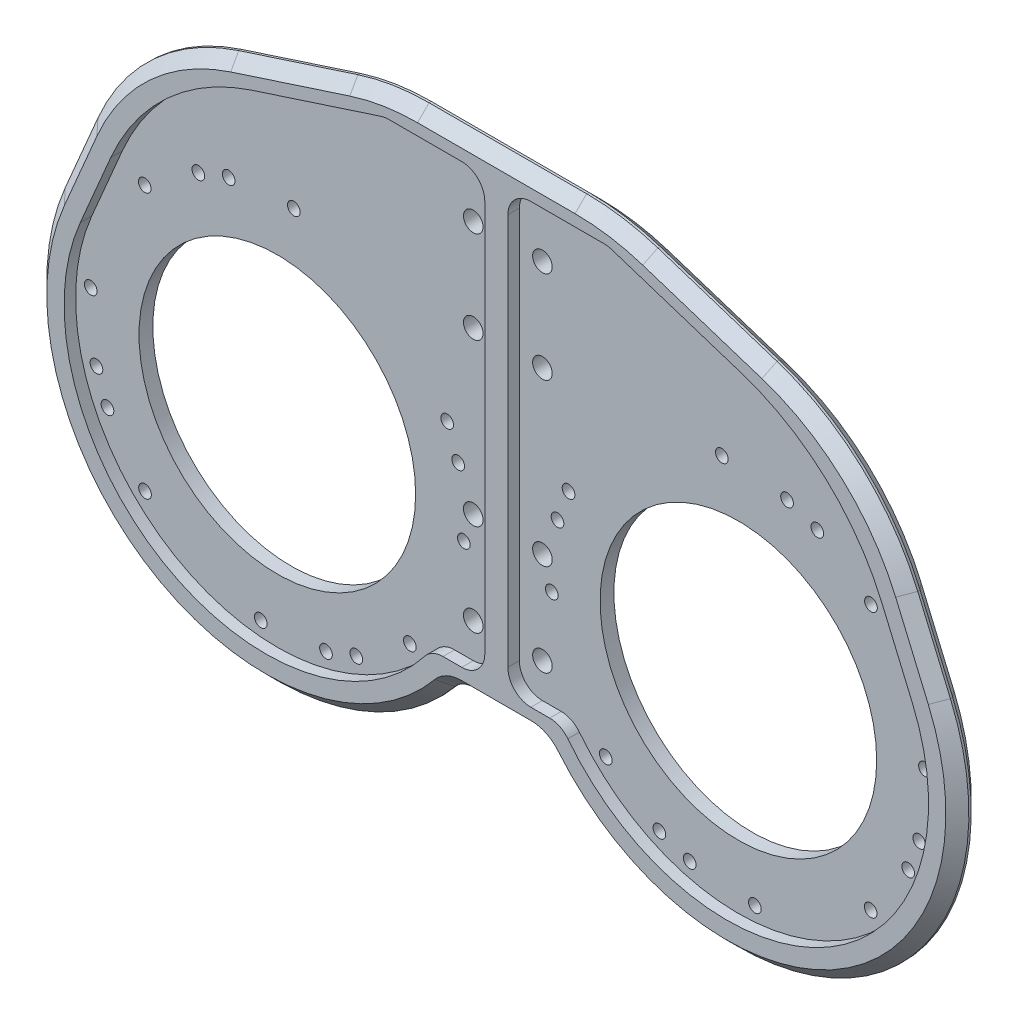
SolidWorks part; units mm, degrees
material "6061 合金"
ref_plane "前视基准面" through (0, 0, 0) normal (0, 0, 1) x (1, 0, 0)
ref_plane "上视基准面" through (0, 0, 0) normal (0, 1, 0) x (1, 0, 0)
ref_plane "右视基准面" through (0, 0, 0) normal (1, 0, 0) x (0, 0, -1)
other "Configuration Table"
sketch "草图1" plane through (0, 0, 0) normal (0, 0, 1) x (1, 0, 0)
  line L0 (0, 0) -> (0, 250) construction
  line L1 (0, 250) -> (769.4209, 0)
  line L3 (769.4209, 0) -> (0, 0)
  line L4 (-50, 352.899) -> (-50, -139.8009) construction
  line L5 (-869.4209, 0) -> (-100, 0)
  line L6 (-100, 250) -> (-869.4209, 0)
  line L7 (-100, 0) -> (-100, 250) construction
  line L8 (-100, 250) -> (0, 250)
  line L9 (0, 0) -> (-100, 0)
  circle A0 centre (50, 100) radius 85 construction
  circle A1 centre (50, 100) radius 60
  circle A2 centre (-150, 100) radius 85 construction
  circle A3 centre (-150, 100) radius 60
  dimension "D1" = 170
  dimension "D4" = 120
  dimension "D2" = 100
  dimension "D3" = 72
  dimension "D5" = 250
  dimension "D6" = 100
  dimension "D7" = 50
extrude "凸台-拉伸1" add sketch "草图1" along normal blind 6 contours L9 L3 L1 L8 L6 L5 A1 A3 region at (-50, 86.7466, 0)
sketch "草图4" plane through (0, 0, 6) normal (0, 0, 1) x (1, 0, 0)
  line L0 (-50, 330.4726) -> (-50, -61.6586) construction
  arc A0 (259.7806, 158.4465) -> (255.249, 156.3335) centre (257.5148, 157.39) ccw construction
  arc A1 (278.6673, 106.1128) -> (283.1989, 108.2258) centre (280.9331, 107.1693) ccw construction
  arc A2 (276.1928, 77.8292) -> (280.7244, 79.9423) centre (278.4586, 78.8857) ccw construction
  arc A3 (271.409, 64.6857) -> (275.9405, 66.7988) centre (273.6748, 65.7423) ccw construction
  arc A4 (255.1242, 41.4287) -> (259.6558, 43.5418) centre (257.39, 42.4852) ccw construction
  arc A5 (204.9035, 18.0104) -> (209.4351, 20.1235) centre (207.1693, 19.0669) ccw construction
  arc A6 (176.62, 20.4849) -> (181.1515, 22.598) centre (178.8857, 21.5414) ccw construction
  arc A7 (163.4765, 25.2687) -> (168.008, 27.3818) centre (165.7423, 26.3252) ccw construction
  arc A8 (140.2194, 41.5535) -> (144.751, 43.6665) centre (142.4852, 42.61) ccw construction
  arc A9 (121.3327, 93.8872) -> (116.8011, 91.7742) centre (119.0669, 92.8307) ccw construction
  arc A10 (123.8072, 122.1708) -> (119.2756, 120.0577) centre (121.5414, 121.1143) ccw construction
  arc A11 (128.591, 135.3143) -> (124.0595, 133.2012) centre (126.3252, 134.2577) ccw construction
  arc A12 (144.8758, 158.5713) -> (140.3442, 156.4582) centre (142.61, 157.5148) ccw construction
  arc A13 (195.0965, 181.9896) -> (190.5649, 179.8765) centre (192.8307, 180.9331) ccw construction
  arc A14 (223.38, 179.5151) -> (218.8485, 177.402) centre (221.1143, 178.4586) ccw construction
  arc A15 (236.5235, 174.7313) -> (231.992, 172.6182) centre (234.2577, 173.6748) ccw construction
  arc A16 (259.7806, 158.4465) -> (255.249, 156.3335) centre (257.5148, 157.39) ccw construction
  arc A17 (278.6673, 106.1128) -> (283.1989, 108.2258) centre (280.9331, 107.1693) ccw construction
  arc A18 (276.1928, 77.8292) -> (280.7244, 79.9423) centre (278.4586, 78.8857) ccw construction
  arc A19 (271.409, 64.6857) -> (275.9405, 66.7988) centre (273.6748, 65.7423) ccw construction
  arc A20 (255.1242, 41.4287) -> (259.6558, 43.5418) centre (257.39, 42.4852) ccw construction
  arc A21 (204.9035, 18.0104) -> (209.4351, 20.1235) centre (207.1693, 19.0669) ccw construction
  arc A22 (176.62, 20.4849) -> (181.1515, 22.598) centre (178.8857, 21.5414) ccw construction
  arc A23 (163.4765, 25.2687) -> (168.008, 27.3818) centre (165.7423, 26.3252) ccw construction
  arc A24 (140.2194, 41.5535) -> (144.751, 43.6665) centre (142.4852, 42.61) ccw construction
  arc A25 (121.3327, 93.8872) -> (116.8011, 91.7742) centre (119.0669, 92.8307) ccw construction
  arc A26 (123.8072, 122.1708) -> (119.2756, 120.0577) centre (121.5414, 121.1143) ccw construction
  arc A27 (128.591, 135.3143) -> (124.0595, 133.2012) centre (126.3252, 134.2577) ccw construction
  arc A28 (144.8758, 158.5713) -> (140.3442, 156.4582) centre (142.61, 157.5148) ccw construction
  arc A29 (195.0965, 181.9896) -> (190.5649, 179.8765) centre (192.8307, 180.9331) ccw construction
  arc A30 (223.38, 179.5151) -> (218.8485, 177.402) centre (221.1143, 178.4586) ccw construction
  arc A31 (236.5235, 174.7313) -> (231.992, 172.6182) centre (234.2577, 173.6748) ccw construction
  circle A32 centre (257.5148, 157.39) radius 2.75
  circle A33 centre (234.2577, 173.6748) radius 2.75
  circle A34 centre (221.1143, 178.4586) radius 2.75
  circle A35 centre (192.8307, 180.9331) radius 2.75
  circle A36 centre (142.61, 157.5148) radius 2.75
  circle A37 centre (126.3252, 134.2577) radius 2.75
  circle A38 centre (121.5414, 121.1143) radius 2.75
  circle A39 centre (119.0669, 92.8307) radius 2.75
  circle A40 centre (142.4852, 42.61) radius 2.75
  circle A41 centre (165.7423, 26.3252) radius 2.75
  circle A42 centre (178.8857, 21.5414) radius 2.75
  circle A43 centre (207.1693, 19.0669) radius 2.75
  circle A44 centre (257.39, 42.4852) radius 2.75
  circle A45 centre (273.6748, 65.7423) radius 2.75
  circle A46 centre (278.4586, 78.8857) radius 2.75
  circle A47 centre (280.9331, 107.1693) radius 2.75
  circle A48 centre (50, 100) radius 60 construction
  circle A49 centre (-150, 100) radius 60 construction
  arc A50 (-336.5235, 174.7313) -> (-331.992, 172.6182) centre (-334.2577, 173.6748) cw construction
  arc A51 (-323.38, 179.5151) -> (-318.8485, 177.402) centre (-321.1143, 178.4586) cw construction
  arc A52 (-295.0965, 181.9896) -> (-290.5649, 179.8765) centre (-292.8307, 180.9331) cw construction
  arc A53 (-244.8758, 158.5713) -> (-240.3442, 156.4582) centre (-242.61, 157.5148) cw construction
  arc A54 (-228.591, 135.3143) -> (-224.0595, 133.2012) centre (-226.3252, 134.2577) cw construction
  arc A55 (-223.8072, 122.1708) -> (-219.2756, 120.0577) centre (-221.5414, 121.1143) cw construction
  arc A56 (-221.3327, 93.8872) -> (-216.8011, 91.7742) centre (-219.0669, 92.8307) cw construction
  arc A57 (-240.2194, 41.5535) -> (-244.751, 43.6665) centre (-242.4852, 42.61) cw construction
  arc A58 (-263.4765, 25.2687) -> (-268.008, 27.3818) centre (-265.7423, 26.3252) cw construction
  arc A59 (-276.62, 20.4849) -> (-281.1515, 22.598) centre (-278.8857, 21.5414) cw construction
  arc A60 (-304.9035, 18.0104) -> (-309.4351, 20.1235) centre (-307.1693, 19.0669) cw construction
  arc A61 (-355.1242, 41.4287) -> (-359.6558, 43.5418) centre (-357.39, 42.4852) cw construction
  arc A62 (-371.409, 64.6857) -> (-375.9405, 66.7988) centre (-373.6748, 65.7423) cw construction
  arc A63 (-376.1928, 77.8292) -> (-380.7244, 79.9423) centre (-378.4586, 78.8857) cw construction
  arc A64 (-378.6673, 106.1128) -> (-383.1989, 108.2258) centre (-380.9331, 107.1693) cw construction
  arc A65 (-359.7806, 158.4465) -> (-355.249, 156.3335) centre (-357.5148, 157.39) cw construction
  circle A66 centre (-380.9331, 107.1693) radius 2.75
  circle A67 centre (-378.4586, 78.8857) radius 2.75
  circle A68 centre (-373.6748, 65.7423) radius 2.75
  circle A69 centre (-357.39, 42.4852) radius 2.75
  circle A70 centre (-307.1693, 19.0669) radius 2.75
  circle A71 centre (-278.8857, 21.5414) radius 2.75
  circle A72 centre (-265.7423, 26.3252) radius 2.75
  circle A73 centre (-242.4852, 42.61) radius 2.75
  circle A74 centre (-219.0669, 92.8307) radius 2.75
  circle A75 centre (-221.5414, 121.1143) radius 2.75
  circle A76 centre (-226.3252, 134.2577) radius 2.75
  circle A77 centre (-242.61, 157.5148) radius 2.75
  circle A78 centre (-292.8307, 180.9331) radius 2.75
  circle A79 centre (-321.1143, 178.4586) radius 2.75
  circle A80 centre (-334.2577, 173.6748) radius 2.75
  circle A81 centre (-357.5148, 157.39) radius 2.75
  dimension "D1" = 5.5
extrude "切除-拉伸2" [suppressed] cut sketch "草图4" against normal blind 10 contours A44 | A45 | A46 | A47 | A32 | A33 | A34 | A35 | A36 | A37 | A38 | A39 | A40 | A41 | A42 | A73 | A72 | A71 | A70 | A69 | A68 | A67 | A66 | A81 | A80 | A79 | A78 | A77 | A76 | A75 | A74 | A43
sketch "草图5" plane through (0, 0, 0) normal (0, 0, -1) x (-1, 0, 0)
  line L0 (50, 354.5789) -> (50, -118.9875) construction
  circle A16 centre (150, 100) radius 60 construction
  circle A17 centre (-50, 100) radius 60 construction
extrude "切除-拉伸3" [suppressed] cut sketch "草图5" against normal blind 5.5
fillet "圆角1" radius 100 2 edges at (-869.4209, 0, 3) (769.4209, 0, 3)
sketch "草图6" plane through (0, 0, 6) normal (0, 0, 1) x (1, 0, 0)
  line L0 (-50, 293.5967) -> (-50, -68.7433) construction
  line L1 (-70, 40) -> (-30, 40)
  line L2 (138.0457, 0) -> (-238.0457, 0) construction
  line L3 (50, 0) -> (-150, 0)
  circle A0 centre (50, 100) radius 85.25 construction
  arc A1 (-30, 40) -> (50, 0) centre (50, 100) ccw
  circle A2 centre (50, 100) radius 60 construction
  circle A3 centre (-150, 100) radius 60 construction
  arc A4 (-70, 40) -> (-150, 0) centre (-150, 100) cw
  dimension "D1" = 170.5
  dimension "D2" = 200
  dimension "D3" = 40
extrude "切除-拉伸4" cut sketch "草图6" against normal blind 10
sketch "草图7" plane through (0, 0, 6) normal (0, 0, 1) x (1, 0, 0)
  line L0 (-50, 316.0763) -> (-50, -100.7481) construction
  line L1 (-150, 0) -> (-238.0457, 0) construction
  line L2 (-241.9905, 139.2142) -> (-210, 214.2588)
  line L3 (-100, 250) -> (-268.9474, 195.1057) construction
  line L4 (-150, 0) -> (-238.0457, 0)
  line L5 (-210, 214.2588) -> (-268.9474, 195.1057)
  line L6 (110, 214.2588) -> (168.9474, 195.1057)
  line L7 (50, 0) -> (138.0457, 0)
  line L8 (141.9905, 139.2142) -> (110, 214.2588)
  arc A0 (-241.9905, 139.2142) -> (-150, 0) centre (-150, 100) ccw
  circle A1 centre (50, 100) radius 60 construction
  circle A2 centre (-150, 100) radius 60 construction
  arc A3 (-268.9474, 195.1057) -> (-238.0457, 0) centre (-238.0457, 100) ccw construction
  arc A4 (-268.9474, 195.1057) -> (-238.0457, 0) centre (-238.0457, 100) ccw
  arc A5 (168.9474, 195.1057) -> (138.0457, 0) centre (138.0457, 100) cw
  arc A6 (141.9905, 139.2142) -> (50, 0) centre (50, 100) cw
  dimension "D1" = 160
extrude "切除-拉伸5" cut sketch "草图7" against normal blind 83
fillet "圆角2" radius 10 2 edges at (-30, 40, 3) (-70, 40, 3)
fillet "圆角3" radius 100 4 edges at (110, 214.2588, 3) (0, 250, 3) (-100, 250, 3) (-210, 214.2588, 3)
sketch "草图8" plane through (0, 0, 6) normal (0, 0, 1) x (1, 0, 0)
  line L0 (-50, 283.5634) -> (-50, -10.7461) construction
  line L1 (-34.8528, 40) -> (-65.1472, 40) construction
  circle A0 centre (-150, 100) radius 60 construction
  circle A1 centre (50, 100) radius 60 construction
  circle A2 centre (-35, 65) radius 4.25
  circle A3 centre (-35, 105) radius 4.25
  circle A4 centre (-35, 175) radius 4.25
  circle A5 centre (-35, 215) radius 4.25
  circle A6 centre (-65, 215) radius 4.25
  circle A7 centre (-65, 175) radius 4.25
  circle A8 centre (-65, 105) radius 4.25
  circle A9 centre (-65, 65) radius 4.25
  dimension "D1" = 8.5
  dimension "D2" = 25
  dimension "D3" = 40
  dimension "D4" = 40
  dimension "D5" = 70
  dimension "D6" = 15
extrude "切除-拉伸6" cut sketch "草图8" against normal blind 10
sketch "草图9" plane through (0, 0, 6) normal (0, 0, 1) x (1, 0, 0)
  line L0 (-50, 299.1056) -> (-50, -13.7223) construction
  line L1 (-45, 50) -> (-21.807, 50)
  line L2 (-45, 240) -> (-1.5838, 240)
  line L3 (-1.5838, 240) -> (99.4298, 207.1787)
  line L4 (99.4298, 207.1787) -> (130.4916, 134.3125)
  line L5 (-34.8528, 40) -> (-65.1472, 40) construction
  line L6 (-84.1616, 250) -> (-15.8384, 250) construction
  line L7 (15.0633, 245.1057) -> (66.7459, 228.3129) construction
  line L8 (127.8347, 172.4215) -> (141.9905, 139.2142) construction
  line L9 (-45, 240) -> (-45, 50)
  line L10 (-55, 240) -> (-55, 50)
  line L11 (-199.4298, 207.1787) -> (-230.4916, 134.3125)
  line L12 (-98.4162, 240) -> (-199.4298, 207.1787)
  line L13 (-55, 240) -> (-98.4162, 240)
  line L14 (-55, 50) -> (-78.193, 50)
  line L21 (141.9905, 139.2142) -> (127.8347, 172.4215)
  line L22 (66.7459, 228.3129) -> (15.0633, 245.1057)
  line L23 (-15.8384, 250) -> (-84.1616, 250)
  line L24 (-115.0633, 245.1057) -> (-166.7459, 228.3129)
  line L25 (-227.8347, 172.4215) -> (-241.9905, 139.2142)
  line L26 (-65.1472, 40) -> (-34.8528, 40)
  line L27 (141.9905, 139.2142) -> (127.8347, 172.4215)
  line L28 (66.7459, 228.3129) -> (15.0633, 245.1057)
  line L29 (-15.8384, 250) -> (-84.1616, 250)
  line L30 (-115.0633, 245.1057) -> (-166.7459, 228.3129)
  line L31 (-227.8347, 172.4215) -> (-241.9905, 139.2142)
  line L32 (-65.1472, 40) -> (-34.8528, 40)
  circle A0 centre (50, 100) radius 87.5 construction
  circle A1 centre (50, 100) radius 60 construction
  circle A2 centre (-150, 100) radius 60 construction
  arc A3 (-21.807, 50) -> (130.4916, 134.3125) centre (50, 100) ccw
  circle A4 centre (-150, 100) radius 87.5 construction
  arc A5 (-78.193, 50) -> (-230.4916, 134.3125) centre (-150, 100) cw
  arc A14 (127.8347, 172.4215) -> (66.7459, 228.3129) centre (35.8442, 133.2073) ccw
  arc A15 (15.0633, 245.1057) -> (-15.8384, 250) centre (-15.8384, 150) ccw
  arc A16 (-84.1616, 250) -> (-115.0633, 245.1057) centre (-84.1616, 150) ccw
  arc A17 (-166.7459, 228.3129) -> (-227.8347, 172.4215) centre (-135.8442, 133.2073) ccw
  arc A18 (-241.9905, 139.2142) -> (-72.8611, 36.3636) centre (-150, 100) ccw
  arc A19 (-65.1472, 40) -> (-72.8611, 36.3636) centre (-65.1472, 30) ccw
  arc A20 (-27.1389, 36.3636) -> (-34.8528, 40) centre (-34.8528, 30) ccw
  arc A21 (-27.1389, 36.3636) -> (141.9905, 139.2142) centre (50, 100) ccw
  arc A22 (127.8347, 172.4215) -> (66.7459, 228.3129) centre (35.8442, 133.2073) ccw
  arc A23 (15.0633, 245.1057) -> (-15.8384, 250) centre (-15.8384, 150) ccw
  arc A24 (-84.1616, 250) -> (-115.0633, 245.1057) centre (-84.1616, 150) ccw
  arc A25 (-166.7459, 228.3129) -> (-227.8347, 172.4215) centre (-135.8442, 133.2073) ccw
  arc A26 (-241.9905, 139.2142) -> (-72.8611, 36.3636) centre (-150, 100) ccw
  arc A27 (-65.1472, 40) -> (-72.8611, 36.3636) centre (-65.1472, 30) ccw
  arc A28 (-27.1389, 36.3636) -> (-34.8528, 40) centre (-34.8528, 30) ccw
  arc A29 (-27.1389, 36.3636) -> (141.9905, 139.2142) centre (50, 100) ccw
  dimension "D1" = 175
  dimension "D2" = 10
  dimension "D3" = 10
  dimension "D4" = 10
  dimension "D5" = 5
  dimension "D6" = 0
extrude "凸台-拉伸2" add sketch "草图9" along normal blind 5
sketch "草图10" plane through (0, 0, 6) normal (0, 0, 1) x (1, 0, 0)
  line L0 (-20, 230) -> (-20, 130)
  line L1 (-20, 130) -> (66.6025, 180)
  line L2 (66.6025, 180) -> (-20, 230)
  line L3 (-50, 285.8782) -> (-50, -42.8226) construction
  line L4 (-15.8384, 250) -> (-84.1616, 250) construction
  line L5 (-166.6025, 180) -> (-80, 230)
  line L6 (-80, 130) -> (-166.6025, 180)
  line L7 (-80, 230) -> (-80, 130)
  circle A0 centre (50, 100) radius 60 construction
  circle A1 centre (-150, 100) radius 60 construction
  dimension "D1" = 30
  dimension "D2" = 20
  dimension "D3" = 100
  dimension "D4" = 100
  dimension "D5" = 100
extrude "切除-拉伸7" [suppressed] cut sketch "草图10" against normal blind 94
fillet "圆角4" [suppressed] radius 10
chamfer "倒角1" [suppressed] distance 5 angle 45
sketch "草图15" plane through (0, 0, 6) normal (0, 0, 1) x (1, 0, 0)
  line L0 (50, 100) -> (41.8993, 191.4878) construction
  line L1 (50, 100) -> (78.1821, 204.738) construction
  line L2 (50, 100) -> (95.9488, 198.8075) construction
  line L3 (50, 100) -> (126.3654, 176.2056) construction
  line L4 (-45, 240) -> (-45, 50) construction
  line L5 (-50, 286.5396) -> (-50, -57.042) construction
  line L6 (-150, 100) -> (-226.3654, 176.2056) construction
  line L7 (-150, 100) -> (-195.9488, 198.8075) construction
  line L8 (-150, 100) -> (-178.1821, 204.738) construction
  line L9 (-150, 100) -> (-141.8993, 191.4878) construction
  circle A0 centre (42.8338, 180.9334) radius 2.75
  circle A1 centre (71.1112, 178.4594) radius 2.75
  circle A2 centre (84.2606, 173.6734) radius 2.75
  circle A3 centre (107.5126, 157.3922) radius 2.75
  circle A4 centre (107.3922, 42.4874) radius 2.75
  circle A5 centre (123.6734, 65.7394) radius 2.75
  circle A6 centre (128.4594, 78.8888) radius 2.75
  circle A7 centre (130.9334, 107.1662) radius 2.75
  circle A8 centre (-7.5126, 42.6078) radius 2.75
  circle A9 centre (15.7394, 26.3266) radius 2.75
  circle A10 centre (28.8888, 21.5406) radius 2.75
  circle A11 centre (57.1662, 19.0666) radius 2.75
  circle A12 centre (-7.3922, 157.5126) radius 2.75 construction
  circle A13 centre (-23.6734, 134.2606) radius 2.75
  circle A14 centre (-28.4594, 121.1112) radius 2.75
  circle A15 centre (-30.9334, 92.8338) radius 2.75
  circle A16 centre (50, 100) radius 60 construction
  circle A17 centre (-150, 100) radius 60 construction
  circle A18 centre (-69.0666, 92.8338) radius 2.75
  circle A19 centre (-71.5406, 121.1112) radius 2.75
  circle A20 centre (-76.3266, 134.2606) radius 2.75
  circle A21 centre (-92.6078, 157.5126) radius 2.75 construction
  circle A22 centre (-157.1662, 19.0666) radius 2.75
  circle A23 centre (-128.8888, 21.5406) radius 2.75
  circle A24 centre (-115.7394, 26.3266) radius 2.75
  circle A25 centre (-92.4874, 42.6078) radius 2.75
  circle A26 centre (-230.9334, 107.1662) radius 2.75
  circle A27 centre (-228.4594, 78.8888) radius 2.75
  circle A28 centre (-223.6734, 65.7394) radius 2.75
  circle A29 centre (-207.3922, 42.4874) radius 2.75
  circle A30 centre (-207.5126, 157.3922) radius 2.75
  circle A31 centre (-184.2606, 173.6734) radius 2.75
  circle A32 centre (-171.1112, 178.4594) radius 2.75
  circle A33 centre (-142.8338, 180.9334) radius 2.75
  point P43 (50, 100)
  point P84 (-150, 100)
  dimension "D9" = 5.5
  dimension "D1" = 5.06
  dimension "D2" = 30
  dimension "D3" = 30
  dimension "D4" = 50.12
  dimension "D5" = 81.25
  dimension "D6" = 81.25
  dimension "D7" = 81.25
  dimension "D8" = 81.25
  dimension "D10" = 4
extrude "切除-拉伸8" cut sketch "草图15" against normal blind 48.5
sketch "草图16" plane through (0, 0, 0) normal (0, 0, -1) x (-1, 0, 0)
  line L0 (50, 280.5872) -> (50, -6.4472) construction
  circle A0 centre (150, 100) radius 60 construction
  circle A1 centre (-50, 100) radius 60 construction
  circle A2 centre (142.8338, 180.9334) radius 6
  circle A3 centre (171.1112, 178.4594) radius 6
  circle A4 centre (184.2606, 173.6734) radius 6
  circle A5 centre (207.5126, 157.3922) radius 6
  circle A6 centre (230.9334, 107.1662) radius 6
  circle A7 centre (228.4594, 78.8888) radius 6
  circle A8 centre (223.6734, 65.7394) radius 6
  circle A9 centre (207.3922, 42.4874) radius 6
  circle A10 centre (157.1662, 19.0666) radius 6
  circle A11 centre (128.8888, 21.5406) radius 6
  circle A12 centre (115.7394, 26.3266) radius 6
  circle A13 centre (92.4874, 42.6078) radius 6
  circle A14 centre (69.0666, 92.8338) radius 6
  circle A15 centre (71.5406, 121.1112) radius 6
  circle A16 centre (76.3266, 134.2606) radius 6
  circle A19 centre (23.6734, 134.2606) radius 6
  circle A20 centre (28.4594, 121.1112) radius 6
  circle A21 centre (30.9334, 92.8338) radius 6
  circle A22 centre (7.5126, 42.6078) radius 6
  circle A23 centre (-15.7394, 26.3266) radius 6
  circle A24 centre (-28.8888, 21.5406) radius 6
  circle A25 centre (-57.1662, 19.0666) radius 6
  circle A26 centre (-107.3922, 42.4874) radius 6
  circle A27 centre (-123.6734, 65.7394) radius 6
  circle A28 centre (-128.4594, 78.8888) radius 6
  circle A29 centre (-130.9334, 107.1662) radius 6
  circle A30 centre (-107.5126, 157.3922) radius 6
  circle A31 centre (-84.2606, 173.6734) radius 6
  circle A32 centre (-71.1112, 178.4594) radius 6
  circle A33 centre (-42.8338, 180.9334) radius 6
  dimension "D1" = 12
extrude "切除-拉伸10" [suppressed] cut sketch "草图16" against normal blind 5.5
fillet "圆角5" radius 10 8 edges at (-78.193, 50, 8.5) (-55, 50, 8.5) (-45, 50, 8.5) (-21.807, 50, 8.5) (-1.5838, 240, 8.5) (-45, 240, 8.5) (-55, 240, 8.5) (-98.4162, 240, 8.5)
fillet "圆角6" radius 100 2 edges at (-199.4298, 207.1787, 8.5) (99.4298, 207.1787, 8.5)
chamfer "倒角2" distance 5 angle 45 28 edges at (134.9126, 155.8179, 11) (103.3467, 206.9868, 11) (101.9587, 14.5582, 11) (40.9046, 236.7093, 11) (-30.5888, 39.0453, 11) (-0.195, 248.7688, 11) (-50, 40, 11) (-50, 250, 11) (-69.4112, 39.0453, 11) (-99.805, 248.7688, 11) (-201.9587, 14.5582, 11) (-140.9046, 236.7093, 11) (-234.9126, 155.8179, 11) (-203.3467, 206.9868, 11) (134.9126, 155.8179, 0) (101.9587, 14.5582, 0) (103.3467, 206.9868, 0) (-30.5888, 39.0453, 0) (40.9046, 236.7093, 0) (-50, 40, 0) (-0.195, 248.7688, 0) (-69.4112, 39.0453, 0) (-50, 250, 0) (-201.9587, 14.5582, 0) (-99.805, 248.7688, 0) (-234.9126, 155.8179, 0) (-140.9046, 236.7093, 0) (-203.3467, 206.9868, 0)
